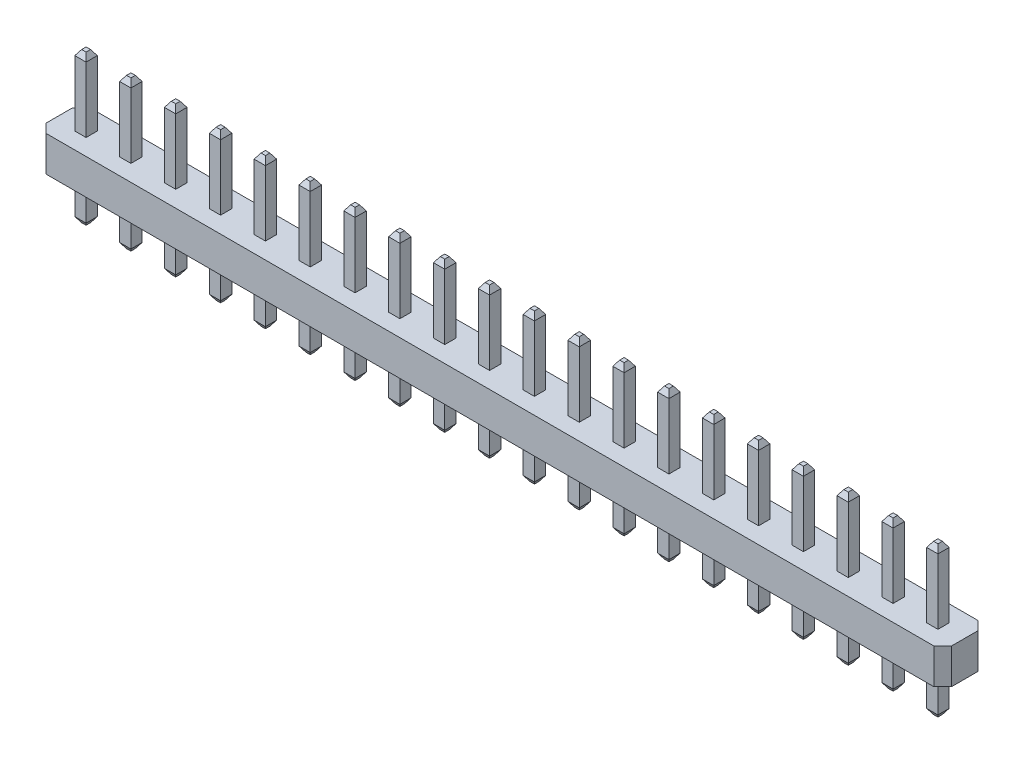
SolidWorks part; units mm, degrees
ref_plane "Front" through (0, 0, 0) normal (0, 0, 1) x (1, 0, 0)
ref_plane "Top" through (0, 0, 0) normal (0, 1, 0) x (1, 0, 0)
ref_plane "Right" through (0, 0, 0) normal (1, 0, 0) x (0, 0, -1)
sketch "Sketch1" plane through (0, 0, 0) normal (0, 1, 0) x (1, 0, 0)
  line L1 (0, 0) -> (51.3, 0)
  line L2 (0, 0) -> (0, 2.5)
  line L3 (0, 2.5) -> (51.3, 2.5)
  line L4 (51.3, 0) -> (51.3, 2.5)
  dimension "D1" = 51.3
  dimension "D2" = 2.5
extrude "Boss-Extrude1" add sketch "Sketch1" along normal blind 2
sketch "Sketch2" plane through (0, 0, 0) normal (0, -1, 0) x (1, 0, 0)
  line L0 (0, 0) -> (51.3, 0) construction
  line L1 (1.2, -0.93) -> (1.84, -0.93)
  line L2 (1.2, -0.93) -> (1.2, -1.57)
  line L3 (1.2, -1.57) -> (1.84, -1.57)
  line L4 (1.84, -0.93) -> (1.84, -1.57)
  line L5 (0, -2.5) -> (0, 0) construction
  line L6 (3.74, -0.93) -> (4.38, -0.93)
  line L7 (3.74, -0.93) -> (3.74, -1.57)
  line L8 (3.74, -1.57) -> (4.38, -1.57)
  line L9 (4.38, -0.93) -> (4.38, -1.57)
  line L10 (6.28, -0.93) -> (6.92, -0.93)
  line L11 (6.28, -0.93) -> (6.28, -1.57)
  line L12 (6.28, -1.57) -> (6.92, -1.57)
  line L13 (6.92, -0.93) -> (6.92, -1.57)
  line L14 (8.82, -0.93) -> (9.46, -0.93)
  line L15 (8.82, -0.93) -> (8.82, -1.57)
  line L16 (8.82, -1.57) -> (9.46, -1.57)
  line L17 (9.46, -0.93) -> (9.46, -1.57)
  line L18 (11.36, -0.93) -> (12, -0.93)
  line L19 (11.36, -0.93) -> (11.36, -1.57)
  line L20 (11.36, -1.57) -> (12, -1.57)
  line L21 (12, -0.93) -> (12, -1.57)
  line L22 (13.9, -0.93) -> (14.54, -0.93)
  line L23 (13.9, -0.93) -> (13.9, -1.57)
  line L24 (13.9, -1.57) -> (14.54, -1.57)
  line L25 (14.54, -0.93) -> (14.54, -1.57)
  line L26 (16.44, -0.93) -> (17.08, -0.93)
  line L27 (16.44, -0.93) -> (16.44, -1.57)
  line L28 (16.44, -1.57) -> (17.08, -1.57)
  line L29 (17.08, -0.93) -> (17.08, -1.57)
  line L30 (18.98, -0.93) -> (19.62, -0.93)
  line L31 (18.98, -0.93) -> (18.98, -1.57)
  line L32 (18.98, -1.57) -> (19.62, -1.57)
  line L33 (19.62, -0.93) -> (19.62, -1.57)
  line L34 (21.52, -0.93) -> (22.16, -0.93)
  line L35 (21.52, -0.93) -> (21.52, -1.57)
  line L36 (21.52, -1.57) -> (22.16, -1.57)
  line L37 (22.16, -0.93) -> (22.16, -1.57)
  line L38 (24.06, -0.93) -> (24.7, -0.93)
  line L39 (24.06, -0.93) -> (24.06, -1.57)
  line L40 (24.06, -1.57) -> (24.7, -1.57)
  line L41 (24.7, -0.93) -> (24.7, -1.57)
  line L42 (26.6, -0.93) -> (27.24, -0.93)
  line L43 (26.6, -0.93) -> (26.6, -1.57)
  line L44 (26.6, -1.57) -> (27.24, -1.57)
  line L45 (27.24, -0.93) -> (27.24, -1.57)
  line L46 (29.14, -0.93) -> (29.78, -0.93)
  line L47 (29.14, -0.93) -> (29.14, -1.57)
  line L48 (29.14, -1.57) -> (29.78, -1.57)
  line L49 (29.78, -0.93) -> (29.78, -1.57)
  line L50 (31.68, -0.93) -> (32.32, -0.93)
  line L51 (31.68, -0.93) -> (31.68, -1.57)
  line L52 (31.68, -1.57) -> (32.32, -1.57)
  line L53 (32.32, -0.93) -> (32.32, -1.57)
  line L54 (34.22, -0.93) -> (34.86, -0.93)
  line L55 (34.22, -0.93) -> (34.22, -1.57)
  line L56 (34.22, -1.57) -> (34.86, -1.57)
  line L57 (34.86, -0.93) -> (34.86, -1.57)
  line L58 (36.76, -0.93) -> (37.4, -0.93)
  line L59 (36.76, -0.93) -> (36.76, -1.57)
  line L60 (36.76, -1.57) -> (37.4, -1.57)
  line L61 (37.4, -0.93) -> (37.4, -1.57)
  line L62 (39.3, -0.93) -> (39.94, -0.93)
  line L63 (39.3, -0.93) -> (39.3, -1.57)
  line L64 (39.3, -1.57) -> (39.94, -1.57)
  line L65 (39.94, -0.93) -> (39.94, -1.57)
  line L66 (41.84, -0.93) -> (42.48, -0.93)
  line L67 (41.84, -0.93) -> (41.84, -1.57)
  line L68 (41.84, -1.57) -> (42.48, -1.57)
  line L69 (42.48, -0.93) -> (42.48, -1.57)
  line L70 (44.38, -0.93) -> (45.02, -0.93)
  line L71 (44.38, -0.93) -> (44.38, -1.57)
  line L72 (44.38, -1.57) -> (45.02, -1.57)
  line L73 (45.02, -0.93) -> (45.02, -1.57)
  line L74 (46.92, -0.93) -> (47.56, -0.93)
  line L75 (46.92, -0.93) -> (46.92, -1.57)
  line L76 (46.92, -1.57) -> (47.56, -1.57)
  line L77 (47.56, -0.93) -> (47.56, -1.57)
  line L78 (49.46, -0.93) -> (50.1, -0.93)
  line L79 (49.46, -0.93) -> (49.46, -1.57)
  line L80 (49.46, -1.57) -> (50.1, -1.57)
  line L81 (50.1, -0.93) -> (50.1, -1.57)
  dimension "D1" = 0.64
  dimension "D2" = 0.64
  dimension "D3" = 0.93
  dimension "D4" = 1.2
  dimension "D5" = 20
extrude "Boss-Extrude2" add sketch "Sketch2" along normal blind 2.5 and the other way blind 6
chamfer "Chamfer1" distance 0.3 angle 33 80 edges at (49.78, -2.5, -0.93) (50.1, -2.5, -1.25) (49.78, -2.5, -1.57) (49.46, -2.5, -1.25) (47.24, -2.5, -0.93) (47.56, -2.5, -1.25) (47.24, -2.5, -1.57) (46.92, -2.5, -1.25) (44.7, -2.5, -0.93) (45.02, -2.5, -1.25) (44.7, -2.5, -1.57) (44.38, -2.5, -1.25) (42.16, -2.5, -0.93) (42.48, -2.5, -1.25) (42.16, -2.5, -1.57) (41.84, -2.5, -1.25) (39.62, -2.5, -0.93) (39.94, -2.5, -1.25) (39.62, -2.5, -1.57) (39.3, -2.5, -1.25) (37.08, -2.5, -0.93) (37.4, -2.5, -1.25) (37.08, -2.5, -1.57) (36.76, -2.5, -1.25) (34.54, -2.5, -0.93) (34.86, -2.5, -1.25) (34.54, -2.5, -1.57) (34.22, -2.5, -1.25) (32, -2.5, -0.93) (32.32, -2.5, -1.25) (32, -2.5, -1.57) (31.68, -2.5, -1.25) (29.46, -2.5, -0.93) (29.78, -2.5, -1.25) (29.46, -2.5, -1.57) (29.14, -2.5, -1.25) (26.92, -2.5, -0.93) (27.24, -2.5, -1.25) (26.92, -2.5, -1.57) (26.6, -2.5, -1.25) (24.38, -2.5, -0.93) (24.7, -2.5, -1.25) (24.38, -2.5, -1.57) (24.06, -2.5, -1.25) (21.84, -2.5, -0.93) (22.16, -2.5, -1.25) (21.84, -2.5, -1.57) (21.52, -2.5, -1.25) (19.3, -2.5, -0.93) (19.62, -2.5, -1.25) (19.3, -2.5, -1.57) (18.98, -2.5, -1.25) (16.76, -2.5, -0.93) (17.08, -2.5, -1.25) (16.76, -2.5, -1.57) (16.44, -2.5, -1.25) (14.22, -2.5, -0.93) (14.54, -2.5, -1.25) (14.22, -2.5, -1.57) (13.9, -2.5, -1.25) (11.68, -2.5, -0.93) (12, -2.5, -1.25) (11.68, -2.5, -1.57) (11.36, -2.5, -1.25) (9.14, -2.5, -0.93) (9.46, -2.5, -1.25) (9.14, -2.5, -1.57) (8.82, -2.5, -1.25) (6.6, -2.5, -0.93) (6.92, -2.5, -1.25) (6.6, -2.5, -1.57) (6.28, -2.5, -1.25) (4.06, -2.5, -0.93) (4.38, -2.5, -1.25) (4.06, -2.5, -1.57) (3.74, -2.5, -1.25) (1.52, -2.5, -0.93) (1.84, -2.5, -1.25) (1.52, -2.5, -1.57) (1.2, -2.5, -1.25)
chamfer "Chamfer2" distance 0.3 angle 33 80 edges at (49.78, 6, -1.57) (50.1, 6, -1.25) (49.78, 6, -0.93) (49.46, 6, -1.25) (47.24, 6, -1.57) (47.56, 6, -1.25) (47.24, 6, -0.93) (46.92, 6, -1.25) (44.7, 6, -1.57) (45.02, 6, -1.25) (44.7, 6, -0.93) (44.38, 6, -1.25) (42.16, 6, -1.57) (42.48, 6, -1.25) (42.16, 6, -0.93) (41.84, 6, -1.25) (39.62, 6, -1.57) (39.94, 6, -1.25) (39.62, 6, -0.93) (39.3, 6, -1.25) (37.08, 6, -1.57) (37.4, 6, -1.25) (37.08, 6, -0.93) (36.76, 6, -1.25) (34.54, 6, -1.57) (34.86, 6, -1.25) (34.54, 6, -0.93) (34.22, 6, -1.25) (32, 6, -1.57) (32.32, 6, -1.25) (32, 6, -0.93) (31.68, 6, -1.25) (29.46, 6, -1.57) (29.78, 6, -1.25) (29.46, 6, -0.93) (29.14, 6, -1.25) (26.92, 6, -1.57) (27.24, 6, -1.25) (26.92, 6, -0.93) (26.6, 6, -1.25) (24.38, 6, -1.57) (24.7, 6, -1.25) (24.38, 6, -0.93) (24.06, 6, -1.25) (21.84, 6, -1.57) (22.16, 6, -1.25) (21.84, 6, -0.93) (21.52, 6, -1.25) (19.3, 6, -1.57) (19.62, 6, -1.25) (19.3, 6, -0.93) (18.98, 6, -1.25) (16.76, 6, -1.57) (17.08, 6, -1.25) (16.76, 6, -0.93) (16.44, 6, -1.25) (14.22, 6, -1.57) (14.54, 6, -1.25) (14.22, 6, -0.93) (13.9, 6, -1.25) (11.68, 6, -1.57) (12, 6, -1.25) (11.68, 6, -0.93) (11.36, 6, -1.25) (9.14, 6, -1.57) (9.46, 6, -1.25) (9.14, 6, -0.93) (8.82, 6, -1.25) (6.6, 6, -1.57) (6.92, 6, -1.25) (6.6, 6, -0.93) (6.28, 6, -1.25) (4.06, 6, -1.57) (4.38, 6, -1.25) (4.06, 6, -0.93) (3.74, 6, -1.25) (1.52, 6, -1.57) (1.84, 6, -1.25) (1.52, 6, -0.93) (1.2, 6, -1.25)
chamfer "Chamfer3" distance 0.5 angle 45 4 edges at (51.3, 1, -2.5) (51.3, 1, 0) (0, 1, -2.5) (0, 1, 0)
